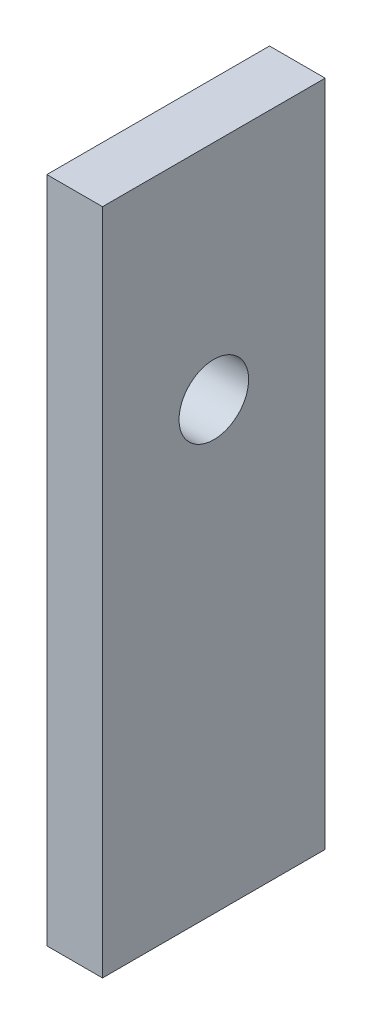
SolidWorks part; units mm, degrees
ref_plane "Front Plane" through (0, 0, 0) normal (0, 0, 1) x (1, 0, 0)
ref_plane "Top Plane" through (0, 0, 0) normal (0, 1, 0) x (1, 0, 0)
ref_plane "Right Plane" through (0, 0, 0) normal (1, 0, 0) x (0, 0, -1)
sketch "Sketch1" plane through (0, 0, 0) normal (1, 0, 0) x (0, 0, -1)
  line L1 (-12.7, 38.1) -> (12.7, 38.1)
  line L2 (-12.7, 38.1) -> (-12.7, -38.1)
  line L3 (-12.7, -38.1) -> (12.7, -38.1)
  line L4 (12.7, 38.1) -> (12.7, -38.1)
  point P4 (-12.9993, 29.2355)
  point P6 (-12.7, 0)
  point P8 (0, -38.1)
  dimension "D1" = 76.2
  dimension "D2" = 25.4
extrude "Boss-Extrude1" add sketch "Sketch1" along normal blind 6.35 contours L2 L3 L4 L1
sketch "Sketch2" plane through (6.35, 0, 0) normal (1, 0, 0) x (0, 0, -1)
  circle A0 centre (0, 12.7) radius 3.9688
  point P2 (0, 0)
  point P3 (4.7811, 12.4879)
  dimension "D1" = 7.9375
  dimension "D2" = 12.7
extrude "Cut-Extrude1" cut sketch "Sketch2" against normal through all both and the other way through all
